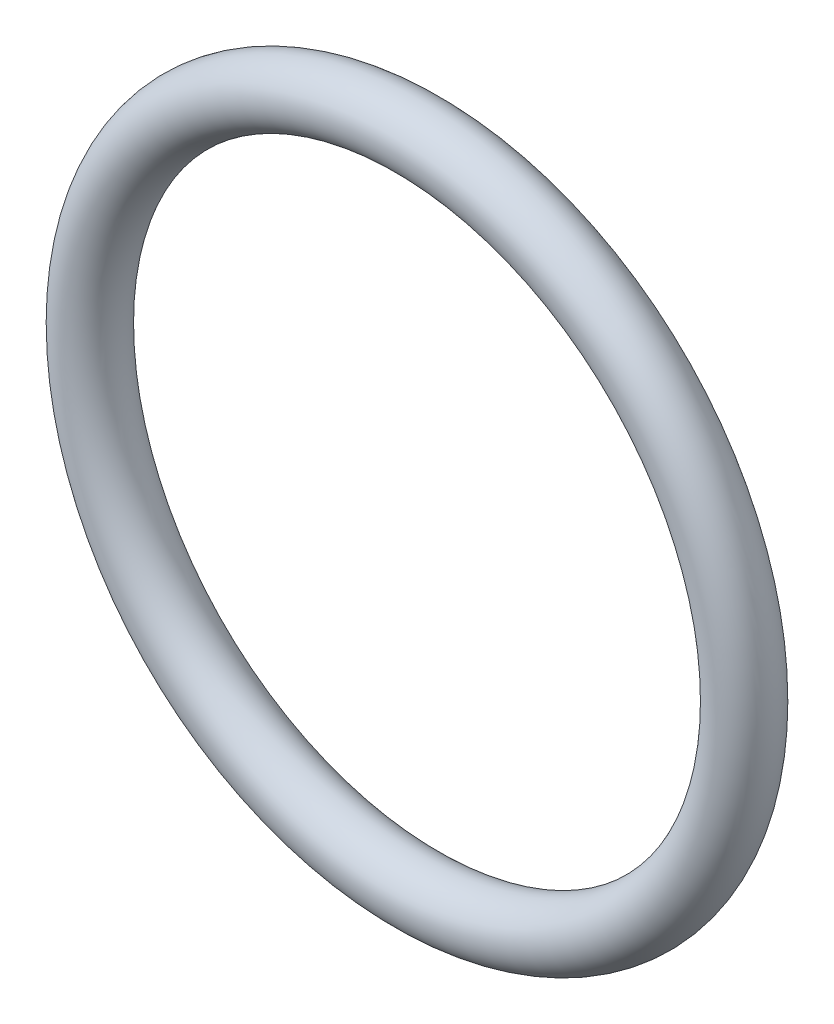
SolidWorks part; units mm, degrees
material "BUNA-N Rubber"
ref_plane "Front" through (0, 0, 0) normal (0, 0, 1) x (1, 0, 0)
ref_plane "Top" through (0, 0, 0) normal (0, 1, 0) x (1, 0, 0)
ref_plane "Right" through (0, 0, 0) normal (1, 0, 0) x (0, 0, -1)
sketch "Sketch1" plane through (0, 0, 0) normal (1, 0, 0) x (0, -1, 0)
  line L0 (0, -1.3081) -> (0, 1.3081) construction
  line L2 (-16.6662, 0) -> (16.6662, 0) construction
  line L3 (-12.5349, 0) -> (12.5349, 0) construction
  circle A0 centre (13.843, 0) radius 1.3081
  point P9 (12.5349, 0)
  point P10 (15.1511, 0)
  point P13 (13.843, 1.3081)
  point P14 (13.843, -1.3081)
  dimension "Width" = 2.6162
  dimension "ID" = 25.0698
revolve "Revolve1" add sketch "Sketch1" angle 360 about L0
ref_axis "Axis1" through (0, 0, 1.4389) along (0, 0, -1)
sketch "Sketch2" plane through (0, 0, 0) normal (0, 0, 1) x (1, 0, 0)
  circle A0 centre (0, 0) radius 12.5349 construction
  circle A1 centre (0, 0) radius 12.5349 construction
